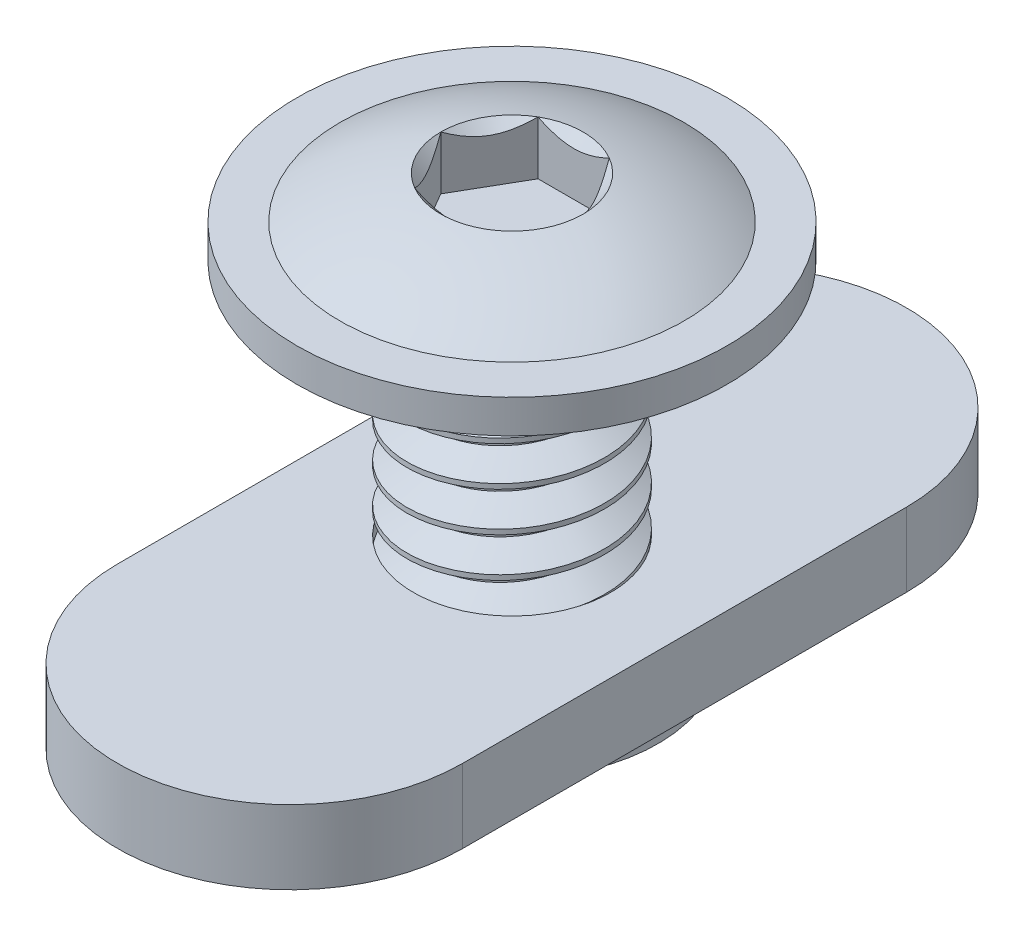
SolidWorks part; units mm, degrees
ref_plane "Front Plane" through (0, 0, 0) normal (0, 0, 1) x (1, 0, 0)
ref_plane "Top Plane" through (0, 0, 0) normal (0, 1, 0) x (1, 0, 0)
ref_plane "Right Plane" through (0, 0, 0) normal (1, 0, 0) x (0, 0, -1)
sketch "Sketch1" plane through (0, 0, 0) normal (0, 0, 1) x (1, 0, 0)
  line L0 (0, 0) -> (0, 53.1234) construction
  line L1 (0, -5.08) -> (-3.175, -5.08)
  line L2 (-3.175, -5.08) -> (-3.175, 5.08)
  line L3 (-3.175, 5.08) -> (-6.9215, 5.08)
  line L4 (-6.9215, 5.08) -> (-6.9215, 6.157)
  line L5 (-6.9215, 6.157) -> (-5.5372, 6.157)
  line L6 (0, -5.08) -> (0, 7.7724)
  arc A0 (-5.5372, 6.157) -> (0, 7.7724) centre (0, -2.5252) cw
  dimension "screw od" = 6.35
  dimension "head od" = 13.843
  dimension "D3" = 11.0744
  dimension "D4" = 1.077
  dimension "head height" = 2.6924
  dimension "screw length" = 10.16
sketch "Sketch2" plane through (0, 0, 0) normal (0, 0, 1) x (1, 0, 0)
  line L0 (0, -5.08) -> (0, 7.7724) construction
  line L1 (-3.175, 5.08) -> (-6.9215, 5.08) construction
  line L2 (0, -5.08) -> (-3.175, -5.08) construction
  line L3 (-3.175, -5.08) -> (-3.175, 5.08) construction
  line L4 (0, -5.08) -> (0, 5.08)
  line L5 (0, 5.08) -> (-3.175, 5.08)
  line L6 (0, -5.08) -> (-3.175, -5.08)
  line L7 (-3.175, -5.08) -> (-3.175, 5.08)
  dimension "D1" = 10.16
revolve "Revolve2" add sketch "Sketch2" angle 360 about L0
sketch "Sketch3" plane through (0, 5.08, 0) normal (0, 1, 0) x (1, 0, 0)
  circle A1 centre (0, 0) radius 3.175
  circle A2 centre (0, 0) radius 3.175
  dimension "D1" = 0
curve "Helix/Spiral1" pitch 1.27 height 14.9225 turns 11.75 parameters "pitch"=1.27
chamfer "Chamfer1" distance 1.27 angle 45 1 edges at (0, -5.08, -3.175)
sketch "Sketch4" plane through (0, 0, 0) normal (0, 0, 1) x (1, 0, 0)
  line L0 (3.175, 6.1912) -> (3.175, 5.08)
  line L1 (3.175, 5.08) -> (2.3501, 5.5562)
  line L2 (2.3501, 5.5562) -> (2.3501, 5.715)
  line L3 (2.3501, 5.715) -> (3.175, 6.1912)
  line L4 (2.3501, 5.6356) -> (3.175, 5.6356) construction
  line L5 (2.7626, 5.3181) -> (2.7626, 5.9531) construction
  line L7 (3.175, 5.08) -> (-3.175, 5.08) construction
  dimension "D1" = 60
  dimension "D2" = 0.1588
  dimension "D3" = 0.635
sweep "Cut-Sweep1" cut profiles "Sketch4" path "Helix/Spiral1"
sketch "Sketch5" plane through (0, 0, 0) normal (0, 0, 1) x (1, 0, 0)
  line L0 (0, -5.08) -> (0, 7.7724) construction
  line L1 (-3.175, 5.08) -> (-6.9215, 5.08) construction
  line L2 (-6.9215, 6.157) -> (-5.5372, 6.157) construction
  line L3 (-6.9215, 5.08) -> (-6.9215, 6.157) construction
  line L4 (0, 5.08) -> (0, 7.7724)
  line L5 (0, 5.08) -> (-6.9215, 5.08)
  line L6 (-6.9215, 6.157) -> (-5.5372, 6.157)
  line L7 (-6.9215, 5.08) -> (-6.9215, 6.157)
  arc A0 (0, 7.7724) -> (-5.5372, 6.157) centre (0, -2.5252) ccw construction
  arc A1 (0, 7.7724) -> (-5.5372, 6.157) centre (0, -2.5252) ccw
revolve "Revolve3" add sketch "Sketch5" angle 360 about L0
ref_plane "Plane1" through (0, 7.7724, 0) normal (0, 1, 0) x (-1, 0, 0)
sketch "Sketch6" plane through (0, 7.7724, 0) normal (0, 1, 0) x (-1, 0, 0)
  line L1 (1.1457, 1.9844) -> (-1.1457, 1.9844)
  line L2 (-1.1457, 1.9844) -> (-2.2914, 0)
  line L3 (-2.2914, 0) -> (-1.1457, -1.9844)
  line L4 (-1.1457, -1.9844) -> (1.1457, -1.9844)
  line L5 (1.1457, -1.9844) -> (2.2914, 0)
  line L6 (2.2914, 0) -> (1.1457, 1.9844)
  circle A0 centre (0, 0) radius 1.9844 construction
  dimension "hex" = 3.9688
extrude "Cut-Extrude1" cut sketch "Sketch6" against normal blind 1.9844
ref_plane "Plane2" through (0, 7.5142, 0) normal (0, 1, 0) x (-1, 0, 0)
sketch "Sketch7" plane through (0, 7.5142, 0) normal (0, 1, 0) x (-1, 0, 0)
  circle A0 centre (0, 0) radius 2.2914
extrude "Cut-Extrude2" cut sketch "Sketch7" against normal up to surface (1.7262 mm away) draft 45 and the other way through all
ref_plane "Plane3" through (0, -4.318, 0) normal (0, -1, 0) x (1, 0, 0)
sketch "Sketch8" plane through (0, -4.318, 0) normal (0, -1, 0) x (1, 0, 0)
  line L0 (0, -7.1437) -> (0, 7.1437) construction
  line L2 (-5.5563, 7.1437) -> (-5.5563, -7.1437)
  line L4 (5.5563, 7.1437) -> (5.5563, -7.1437)
  circle A0 centre (0, 0) radius 3.175
  arc A1 (-5.5563, 7.1437) -> (5.5563, 7.1437) centre (0, 7.1437) cw
  arc A2 (-5.5563, -7.1437) -> (5.5563, -7.1437) centre (0, -7.1437) ccw
  dimension "D1" = 6.35
  dimension "D3" = 25.4
  dimension "D2" = 11.1125
extrude "Extrude1" add sketch "Sketch8" along normal mid plane 3.4544 separate body
sketch "Sketch9" plane through (0, -6.0452, 0) normal (0, -1, 0) x (1, 0, 0)
  line L2 (5.5563, -7.1437) -> (5.5563, 7.1437)
  line L3 (-5.5563, 7.1437) -> (-5.5563, -7.1437)
  line L4 (5.5563, -7.1437) -> (5.5563, 7.1437)
  line L5 (-5.5563, 7.1437) -> (-5.5563, -7.1437)
  arc A2 (-5.5563, -7.1437) -> (5.5563, -7.1437) centre (0, -7.1437) ccw
  arc A3 (5.5563, 7.1437) -> (-5.5563, 7.1437) centre (0, 7.1437) ccw
  arc A4 (-5.5563, -7.1437) -> (5.5563, -7.1437) centre (0, -7.1437) ccw
  arc A5 (5.5563, 7.1437) -> (-5.5563, 7.1437) centre (0, 7.1437) ccw
  circle A6 centre (0, 0) radius 4.699
  circle A7 centre (0, 0) radius 4.699
  dimension "D1" = 0
  dimension "D2" = 1.524
extrude "Cut-Extrude3" cut sketch "Sketch9" against normal offset from surface (1.0795 mm away) 2.3749 up to face at (0, -2.5908, 0)
sketch "Sketch10" [suppressed] plane through (0, 7.9375, 0) normal (0, -1, 0) x (1, 0, 0)
  line L0 (-8.255, -12.3888) -> (-8.255, 2.8511)
  line L1 (8.255, 2.8511) -> (8.255, -12.3888)
  line L2 (-14.9844, 7.9311) -> (0, 7.9311) construction
  circle A0 centre (0, 0) radius 3.9688
  arc A1 (8.255, 2.8511) -> (-8.255, 2.8511) centre (0, -1.316) ccw
  arc A2 (-8.255, -12.3888) -> (8.255, -12.3888) centre (0, -8.2217) ccw
  dimension "D2" = 3.9624
  dimension "D3" = 16.51
  dimension "D4" = 5.08
  dimension "D5" = 6.35
  dimension "D1" = 25.4
extrude "Extrude2" [suppressed] add sketch "Sketch10" along normal mid plane 5.3594 separate body
sketch "Sketch11" [suppressed] plane through (0, 5.2578, 0) normal (0, -1, 0) x (1, 0, 0)
  line L2 (8.255, -12.3888) -> (8.255, 2.8511)
  line L3 (-8.255, 2.8512) -> (-8.255, -12.3888)
  line L4 (8.255, -12.3888) -> (8.255, 2.8511)
  line L5 (-8.255, 2.8512) -> (-8.255, -12.3888)
  circle A2 centre (0, 0) radius 5.4927
  circle A3 centre (0, 0) radius 5.4927
  arc A5 (-8.255, -12.3888) -> (8.255, -12.3888) centre (0, -8.2217) ccw
  arc A6 (8.255, 2.8511) -> (-8.255, 2.8512) centre (0, -1.316) ccw
  arc A7 (-8.255, -12.3888) -> (8.255, -12.3888) centre (0, -8.2217) ccw
  arc A8 (8.255, 2.8511) -> (-8.255, 2.8512) centre (0, -1.316) ccw
  dimension "D1" = 1.524
  dimension "D2" = 0
extrude "Cut-Extrude4" [suppressed] cut sketch "Sketch11" against normal offset from surface (1.651 mm away) 3.7084
sketch "Sketch12" [suppressed] plane through (0, 0, 0) normal (0, 0, 1) x (1, 0, 0)
  line L0 (-6.7564, 17.78) -> (-5.4051, 17.78) construction
  line L1 (-6.7564, 17.78) -> (-5.4051, 17.78)
  line L2 (10.3378, 20.0315) -> (-10.3378, 20.0315) construction
  line L3 (0, 0) -> (0, 53.1234) construction
  line L4 (-3.9688, 15.875) -> (-6.7564, 15.875) construction
  line L5 (-9.398, 15.875) -> (-3.9688, 15.875)
  line L6 (-9.398, 15.875) -> (-9.398, 14.605)
  line L7 (-9.398, 14.605) -> (-3.9688, 14.605)
  line L8 (-3.9688, 15.875) -> (-3.9688, 14.605)
  arc A0 (0, 20.6375) -> (-5.4051, 17.78) centre (0, 14.0967) ccw construction
  arc A1 (-2.7496, 20.0315) -> (-5.4051, 17.78) centre (0, 14.0967) ccw
  arc A2 (-6.7564, 17.78) -> (-2.7496, 20.0315) centre (0, 10.4472) cw
  dimension "D1" = 9.398
  dimension "D2" = 1.27
revolve "Revolve4" [suppressed] add sketch "Sketch12" angle 360 about L0
sketch "Sketch13" [suppressed] plane through (0, 6.35, 0) normal (0, -1, 0) x (1, 0, 0)
  line L0 (-7.9375, 4.7562) -> (-7.9375, -17.4688)
  line L1 (7.9375, 4.7562) -> (7.9375, -17.4688)
  circle A0 centre (0, 0) radius 3.9688
  arc A1 (-7.9375, 4.7562) -> (7.9375, 4.7562) centre (0, -3.5782) cw
  arc A2 (-7.9375, -17.4688) -> (7.9375, -17.4688) centre (0, -9.1345) ccw
  dimension "D2" = 28.575
  dimension "D3" = 3.9624
  dimension "D4" = 7.9375
  dimension "D1" = 15.875
  dimension "D5" = 3.175
extrude "Extrude4" [suppressed] add sketch "Sketch13" along normal mid plane 5.8928 separate body
sketch "Sketch14" [suppressed] plane through (0, 3.4036, 0) normal (0, -1, 0) x (1, 0, 0)
  line L2 (-7.9375, 4.7561) -> (-7.9375, -17.4688)
  line L3 (7.9375, -17.4688) -> (7.9375, 4.7562)
  line L4 (-7.9375, 4.7561) -> (-7.9375, -17.4688)
  line L5 (7.9375, -17.4688) -> (7.9375, 4.7562)
  arc A2 (7.9375, 4.7562) -> (-7.9375, 4.7561) centre (0, -3.5782) ccw
  arc A3 (-7.9375, -17.4688) -> (7.9375, -17.4688) centre (0, -9.1345) ccw
  arc A4 (7.9375, 4.7562) -> (-7.9375, 4.7561) centre (0, -3.5782) ccw
  arc A5 (-7.9375, -17.4688) -> (7.9375, -17.4688) centre (0, -9.1345) ccw
  circle A6 centre (0, 0) radius 5.4927
  circle A7 centre (0, 0) radius 5.4927
  dimension "D1" = 0
  dimension "D2" = 1.524
extrude "Cut-Extrude7" [suppressed] cut sketch "Sketch14" against normal offset from surface (1.8034 mm away) 4.0894
sketch "Sketch15" [suppressed] plane through (0, 0, 0) normal (0, 0, 1) x (1, 0, 0)
  line L0 (-6.6675, 19.6774) -> (-5.334, 19.6774) construction
  line L1 (-6.6675, 19.6774) -> (-5.334, 19.6774)
  line L2 (9.2481, 22.5402) -> (-9.2481, 22.5402) construction
  line L3 (0, 0) -> (0, 53.1234) construction
  arc A0 (0, 22.9997) -> (-5.334, 19.6774) centre (0, 17.0567) ccw construction
  arc A1 (-2.2914, 22.5402) -> (-5.334, 19.6774) centre (0, 17.0567) ccw
  arc A2 (-2.2914, 22.5402) -> (-6.6675, 19.6774) centre (0, 14.2615) ccw
revolve "Revolve5" [suppressed] add sketch "Sketch15" angle 360 about L0
sketch "Sketch16" [suppressed] plane through (0, 3.175, 0) normal (0, -1, 0) x (1, 0, 0)
  line L0 (-6.3881, 8.443) -> (-6.3881, -33.843)
  line L1 (6.3881, 8.443) -> (6.3881, -33.843)
  line L2 (0, -25.4) -> (0, 0) construction
  line L3 (0, -12.7) -> (-6.3881, -12.7) construction
  line L4 (-6.3881, -27.1355) -> (-6.3881, 1.7355) construction
  circle A0 centre (0, 0) radius 3.175
  circle A1 centre (0, -25.4) radius 3.175
  arc A2 (-6.3881, 8.443) -> (6.3881, 8.443) centre (0, 1.7355) cw
  arc A3 (-6.3881, -33.843) -> (6.3881, -33.843) centre (0, -27.1355) ccw
  dimension "D1" = 25.4
  dimension "D2" = 6.35
  dimension "D4" = 47.3964
  dimension "D3" = 12.7762
  dimension "D5" = 2.5552
extrude "Extrude5" [suppressed] add sketch "Sketch16" along normal mid plane 4.0894 separate body
sketch "Sketch17" [suppressed] plane through (0, 1.1303, 0) normal (0, -1, 0) x (1, 0, 0)
  line L2 (-6.3881, 8.443) -> (-6.3881, -33.843)
  line L3 (6.3881, -33.843) -> (6.3881, 8.443)
  line L4 (-6.3881, 8.443) -> (-6.3881, -33.843)
  line L5 (6.3881, -33.843) -> (6.3881, 8.443)
  arc A2 (6.3881, 8.443) -> (-6.3881, 8.443) centre (0, 1.7355) ccw
  arc A3 (-6.3881, -33.843) -> (6.3881, -33.843) centre (0, -27.1355) ccw
  arc A4 (6.3881, 8.443) -> (-6.3881, 8.443) centre (0, 1.7355) ccw
  arc A5 (-6.3881, -33.843) -> (6.3881, -33.843) centre (0, -27.1355) ccw
  circle A6 centre (0, -25.4) radius 4.699
  circle A7 centre (0, -25.4) radius 4.699
  circle A10 centre (0, 0) radius 4.699
  circle A11 centre (0, 0) radius 4.699
  dimension "D1" = 0
  dimension "D2" = 1.524
  dimension "D3" = 1.524
pattern_linear "LPattern1" [suppressed] count 2 spacing 25.4
extrude "Cut-Extrude9" [suppressed] cut sketch "Sketch17" against normal offset from surface (1.4224 mm away) 2.667
sketch "Sketch18" [suppressed] plane through (0, 7.9375, 0) normal (0, -1, 0) x (1, 0, 0)
  line L0 (-7.9375, 13.462) -> (-7.9375, -51.562)
  line L1 (7.9375, 13.462) -> (7.9375, -51.562)
  line L2 (0, 0) -> (0, -38.1) construction
  line L3 (0, -19.05) -> (-7.9375, -19.05) construction
  line L4 (0, -19.05) -> (7.9375, -19.05) construction
  circle A0 centre (0, 0) radius 3.9688
  circle A1 centre (0, -38.1) radius 3.9688
  arc A2 (-7.9375, 13.462) -> (7.9375, 13.462) centre (0, 5.1276) cw
  arc A3 (-7.9375, -51.562) -> (7.9375, -51.562) centre (0, -43.2276) ccw
  dimension "D1" = 38.1
  dimension "D2" = 7.9375
  dimension "D4" = 3.175
  dimension "D5" = 71.374
  dimension "D3" = 15.875
extrude "Extrude6" [suppressed] add sketch "Sketch18" along normal mid plane 5.9944 separate body
sketch "Sketch19" [suppressed] plane through (0, 4.9403, 0) normal (0, -1, 0) x (1, 0, 0)
  line L2 (-7.9375, 13.462) -> (-7.9375, -51.562)
  line L3 (7.9375, -51.562) -> (7.9375, 13.462)
  line L4 (-7.9375, 13.462) -> (-7.9375, -51.562)
  line L5 (7.9375, -51.562) -> (7.9375, 13.462)
  arc A2 (7.9375, 13.462) -> (-7.9375, 13.462) centre (0, 5.1276) ccw
  arc A3 (-7.9375, -51.562) -> (7.9375, -51.562) centre (0, -43.2276) ccw
  arc A4 (7.9375, 13.462) -> (-7.9375, 13.462) centre (0, 5.1276) ccw
  arc A5 (-7.9375, -51.562) -> (7.9375, -51.562) centre (0, -43.2276) ccw
  circle A6 centre (0, 0) radius 5.4927
  circle A7 centre (0, 0) radius 5.4927
  circle A9 centre (0, -38.1) radius 5.4928
  circle A10 centre (0, -38.1) radius 5.4928
  dimension "D1" = 0
  dimension "D2" = 1.524
  dimension "D3" = 1.524
extrude "Cut-Extrude10" [suppressed] cut sketch "Sketch19" against normal offset from surface (2.1844 mm away) 3.81
pattern_linear "LPattern2" [suppressed] count 2 spacing 38.1
equation "\"D2@Sketch4\" = \"pitch@Helix/Spiral1\"*.125"
equation "\"D3@Sketch4\" = \"pitch@Helix/Spiral1\"*.5"
equation "\"D3@Helix/Spiral1\" = \"screw length@Sketch1\"+.18750"
equation "\"D1@Chamfer1\" = \"pitch@Helix/Spiral1\""
equation "\"D1@Cut-Extrude1\" = \"hex@Sketch6\"/2"
equation "\"D1@Sketch8\" = \"screw od@Sketch1\""
equation "\"D4@Sketch1\" = \"head height@Sketch1\"/2.5"
equation "\"D3@Sketch1\" = \"head od@Sketch1\"*.8"
equation "\"D5@Sketch10\" = \"screw od@Sketch1\""
equation "\"D4@Sketch10\" = \"D1@Sketch10\"*.2"
equation "\"D5@Sketch13\" = \"D1@Sketch13\"*.2"
equation "\"D5@Sketch16\" = \"D3@Sketch16\"*.2"
equation "\"D4@Sketch18\" = \"D3@Sketch18\"*.2"
